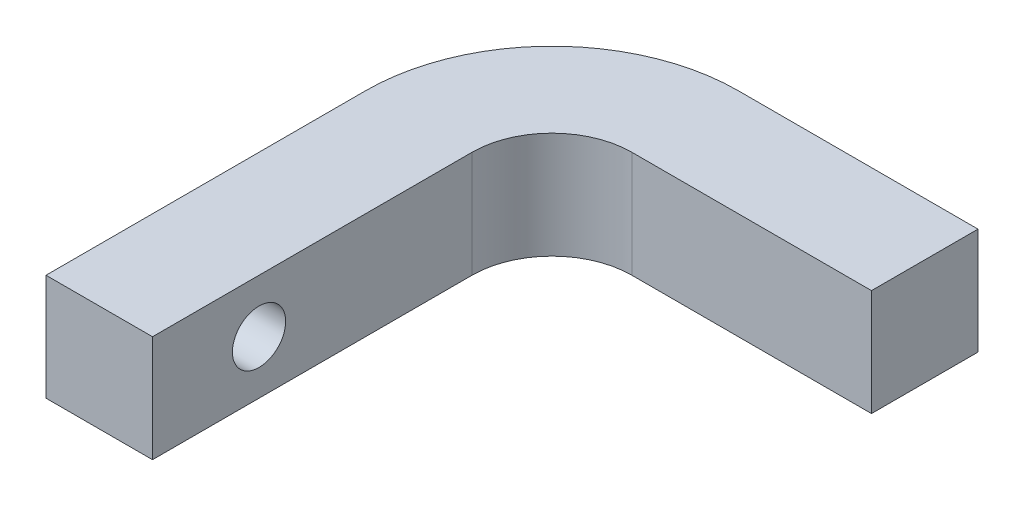
SolidWorks part; units mm, degrees
ref_plane "Front Plane" through (0, 0, 0) normal (0, 0, 1) x (1, 0, 0)
ref_plane "Top Plane" through (0, 0, 0) normal (0, 1, 0) x (1, 0, 0)
ref_plane "Right Plane" through (0, 0, 0) normal (1, 0, 0) x (0, 0, -1)
ref_axis "Z" through (0, 0, -1.9) along (0, 0, 1)
sketch "Sketch1" plane through (0, 0, 0) normal (0, 1, 0) x (1, 0, 0)
  line L0 (-9, 0) -> (9, 0)
  line L1 (-23, -14) -> (-23, -38)
  line L2 (-23, -38) -> (-15, -38)
  line L3 (-15, -38) -> (-15, -14)
  line L4 (-9, -8) -> (9, -8)
  line L5 (0, -8) -> (0, 0) construction
  line L6 (15, -38) -> (15, -14) construction
  line L7 (23, -38) -> (15, -38) construction
  line L8 (23, -14) -> (23, -38) construction
  line L9 (9, 0) -> (9, -8)
  arc A0 (-9, 0) -> (-23, -14) centre (-9, -14) ccw
  arc A1 (-15, -14) -> (-9, -8) centre (-9, -14) cw
  arc A2 (15, -14) -> (9, -8) centre (9, -14) ccw construction
  arc A3 (9, 0) -> (23, -14) centre (9, -14) cw construction
  dimension "D3" = 6
  dimension "D1" = 30
  dimension "D2" = 8
  dimension "D4" = 30
extrude "Boss-Extrude1" add sketch "Sketch1" along normal blind 4 and the other way blind 4
sketch "Sketch2" plane through (-15, 0, 0) normal (-1, 0, 0) x (0, 0, 1)
  line L1 (17.6, 0) -> (-17.6, 0) construction
  line L2 (0, -4.4) -> (0, 4.4) construction
  circle A0 centre (30, 0) radius 2
  dimension "D1" = 4
  dimension "D2" = 30
extrude "Cut-Extrude1" cut sketch "Sketch2" against normal through all both and the other way through all
ref_axis "Axis2" through (-56.6767, 0, 30) along (1, 0, 0)
equation "\"width\"= \"EyeDiameter\" + \"EyeClearance\""
equation "\"prongwidth\"= 8"
equation "\"D2@Sketch1\"=\"prongwidth\""
equation "\"D3@Sketch1\"=\"width\"/5"
equation "\"pronglength\"= \"BasePlaneDistance\"'model implicitly adds clearance (of prongwidth) to the hole drilled at the baseplanedistance"
equation "\"D4@Sketch1\"=\"pronglength\""
equation "\"D1@Boss-Extrude1\"=\"prongwidth\"/2"
equation "\"D2@Boss-Extrude1\"=\"prongwidth\"/2"
equation "\"lbracket-plane-to-axis\"= \"BasePlaneDistance\""
equation "\"D2@Sketch2\"=\"lbracket-plane-to-axis\""
equation "\"EyeDiameter\" = 28"
equation "\"BasePlaneDistance\" = 30"
equation "\"EyeClearance\" = 2"
